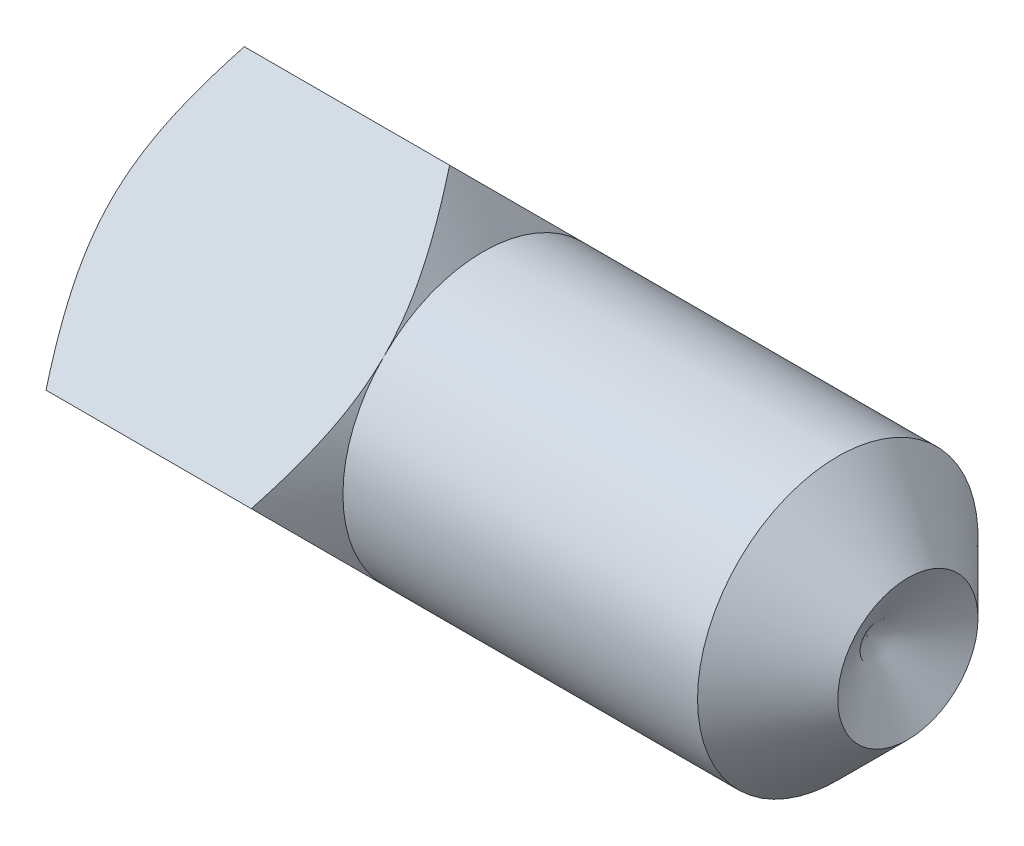
SolidWorks part; units mm, degrees
ref_plane "Front Plane" through (0, 0, 0) normal (0, 0, 1) x (1, 0, 0)
ref_plane "Top Plane" through (0, 0, 0) normal (0, 1, 0) x (1, 0, 0)
ref_plane "Right Plane" through (0, 0, 0) normal (1, 0, 0) x (0, 0, -1)
sketch "BaseHeadSke" plane through (0, 0, 0) normal (1, 0, 0) x (0, 0, -1)
  line L0 (0, 0) -> (14.1701, 0) construction
  line L1 (0, 0) -> (0, 11.9761) construction
  line L2 (0, 2.8284) -> (2.8284, 0)
  line L3 (0, -2.8284) -> (2.8284, 0)
  line L4 (0, 2.8284) -> (-2.8284, 0)
  line L5 (0, -2.8284) -> (-2.8284, 0)
  dimension "D1" = 45
  dimension "Width_flats" = 4
extrude "BaseHead" add sketch "BaseHeadSke" along normal blind 4
sketch "HeadChamferSke" plane through (0, 0, 0) normal (0, 0, 1) x (1, 0, 0)
  line L0 (0, 0) -> (6.1973, 0) construction
  line L1 (2, 2.8284) -> (2, -3.5627) construction
  line L2 (4, 2.8284) -> (0, 2.8284) construction
  line L3 (0, 2.8284) -> (0, 1.9)
  line L4 (0, 2.8284) -> (0.536, 2.8284)
  line L5 (0.536, 2.8284) -> (0, 1.9)
  line L6 (0, 2.8284) -> (0, 0) construction
  line L7 (3.464, 2.8284) -> (4, 1.9)
  line L8 (4, 2.8284) -> (3.464, 2.8284)
  line L9 (4, 2.8284) -> (4, 1.9)
  dimension "Head_chamfer" = 3.8
  dimension "Angle" = 30
revolve "HeadChamfer" cut sketch "HeadChamferSke" angle 360 about L0
sketch "BodySke" plane through (0, 0, 0) normal (0, 0, 1) x (1, 0, 0)
  line L0 (0, 0) -> (13.1857, 0) construction
  line L1 (4, -1.9) -> (4, 1.9) construction
  line L2 (4, 0) -> (4, 1.9) construction
  line L3 (3.464, 2) -> (10, 2)
  line L4 (10, 2) -> (10, 0)
  line L5 (4, 1.9) -> (4, 2) construction
  line L6 (3.464, 2) -> (3.464, 0)
  line L7 (3.464, 0) -> (10, 0)
  line L8 (9.3, 4.69) -> (9.3, -2.048) construction
  point P9 (3.464, 1.61)
  dimension "Minor_dia" = 3.22
  dimension "Advance" = 0.7
revolve "BaseBody" add sketch "BodySke" angle 360 about L0
cosmetic thread "ThreadCosmetic" [suppressed] parameters "Minor_dia"=3.22
sketch "ChamferEndSke" plane through (0, 0, 0) normal (0, 0, 1) x (1, 0, 0)
  line L0 (0, 0) -> (11.9528, 0) construction
  line L1 (10, 2) -> (10, 1)
  line L2 (10, 1) -> (9, 2)
  line L3 (9, 2) -> (10, 2)
  line L4 (10, 2) -> (3.9423, 2) construction
  line L5 (10, -2) -> (10, 2) construction
  dimension "D1" = 45
revolve "ChamferEnd" cut sketch "ChamferEndSke" angle 360 about L0
sketch "ThdSchSke" plane through (0, 0, 0) normal (0, 0, 1) x (1, 0, 0)
  line L0 (8.3, 2.4503) -> (8.3, 2)
  line L1 (8.3, 2.4503) -> (8.7503, 2.4503)
  line L2 (8.7503, 2.4503) -> (8.7503, 2)
  line L3 (8.7503, 2) -> (8.5252, 1.61)
  line L4 (8.5252, 1.61) -> (8.3, 2)
  line L5 (0, 0) -> (11.8711, 0) construction
  line L6 (9, 2) -> (3.9423, 2) construction
  dimension "D1" = 0.7
revolve "ThreadSchematic" [suppressed] cut sketch "ThdSchSke" angle 360 about L5
pattern_linear "ThdSchPat" [suppressed] count 6 of bodies 105
sketch "CupPointSke" plane through (0, 0, 0) normal (0, 0, 1) x (1, 0, 0)
  line L0 (0, 0) -> (12.971, 0) construction
  line L1 (10, 1) -> (9.4226, 0)
  line L3 (10, 1) -> (10, 0)
  line L4 (10, -1) -> (10, 1) construction
  line L5 (10, 0) -> (9.4226, 0)
  dimension "D1" = 60
revolve "CupPoint" cut sketch "CupPointSke" angle 360 about L0
equation "\"Minor_dia@ThreadCosmetic\" = \"Minor_dia@BodySke\""
equation "\"D1@ThdSchSke\" = \"Advance@BodySke\""
equation "\"Advance@ThdSchPat\" = \"Advance@BodySke\""
equation "\"D1@ThdSchPat\" =  int( (  \"Length@BodySke\" -  ( \"Diameter@BodySke\" - \"End_chamfer@ChamferEndSke\" )  / 2 )  /\"Advance@ThdSchPat\" )  - 1"
